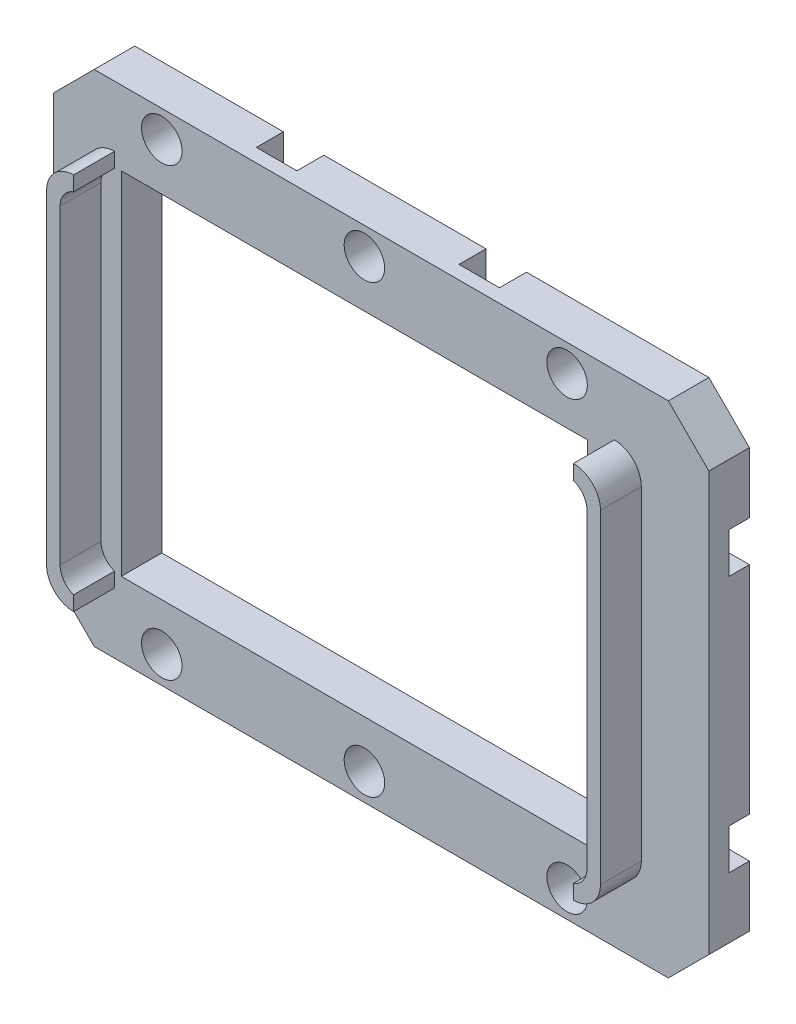
SolidWorks part; units mm, degrees
ref_plane "前视基准面" through (0, 0, 0) normal (0, 0, 1) x (1, 0, 0)
ref_plane "上视基准面" through (0, 0, 0) normal (0, 1, 0) x (1, 0, 0)
ref_plane "右视基准面" through (0, 0, 0) normal (1, 0, 0) x (0, 0, -1)
ref_plane "基准面4" through (0, 0, -11) normal (0, 0, 1) x (1, 0, 0)
sketch "草图1" plane through (0, 0, -11) normal (0, 0, 1) x (1, 0, 0)
  line L0 (-23, -18.5) -> (25.5, -18.5)
  line L1 (25.5, -18.5) -> (25.5, 18.5)
  line L2 (25.5, 18.5) -> (-23, 18.5)
  line L3 (-23, 18.5) -> (-23, -18.5)
extrude "凸台-拉伸1" add sketch "草图1" against normal blind 3
sketch "草图2" plane through (0, 0, -14) normal (0, 0, -1) x (-1, 0, 0)
  line L0 (17.5, -13.0002) -> (17.5, -10.2132)
  line L1 (17.5, -10.2132) -> (-4.4207, -10.2132)
  line L2 (-4.4207, -10.2132) -> (-4.4207, -13.0002)
  line L3 (-4.4207, -13.0002) -> (17.5, -13.0002)
extrude "切除-拉伸1" cut sketch "草图2" against normal through all
sketch "草图6" plane through (0, 0, -14) normal (0, 0, -1) x (-1, 0, 0)
  line L0 (-4.4207, 13.0002) -> (-4.4207, 10.2132)
  line L1 (-4.4207, 10.2132) -> (17.5, 10.2132)
  line L2 (17.5, 10.2132) -> (17.5, 13.0002)
  line L3 (17.5, 13.0002) -> (-4.4207, 13.0002)
extrude "切除-拉伸5" cut sketch "草图6" against normal through all
sketch "草图7" plane through (0, 0, -11) normal (0, 0, 1) x (1, 0, 0)
  line L0 (-20.5, -12) -> (-20.5, 12)
  line L1 (-18.5, 14) -> (-18.5, 12.9142)
  line L2 (-19.5, 11.5) -> (-19.5, -11.5)
  line L3 (-18.5, -12.9142) -> (-18.5, -14)
  arc A0 (-18.5, -14) -> (-20.5, -12) centre (-18.5, -12) cw
  arc A1 (-20.5, 12) -> (-18.5, 14) centre (-18.5, 12) cw
  arc A2 (-18.5, 12.9142) -> (-19.5, 11.5) centre (-18, 11.5) ccw
  arc A3 (-19.5, -11.5) -> (-18.5, -12.9142) centre (-18, -11.5) ccw
extrude "凸台-拉伸2" add sketch "草图7" along normal blind 3.028
sketch "草图8" plane through (0, 0, -11) normal (0, 0, 1) x (1, 0, 0)
  line L0 (19.5, -11.5) -> (19.5, 11.5)
  line L1 (18.5, 12.9142) -> (18.5, 14)
  line L2 (20.5, 12) -> (20.5, -12)
  line L3 (18.5, -14) -> (18.5, -12.9142)
  arc A0 (18.5, -12.9142) -> (19.5, -11.5) centre (18, -11.5) ccw
  arc A1 (19.5, 11.5) -> (18.5, 12.9142) centre (18, 11.5) ccw
  arc A2 (18.5, 14) -> (20.5, 12) centre (18.5, 12) cw
  arc A3 (20.5, -12) -> (18.5, -14) centre (18.5, -12) cw
extrude "凸台-拉伸3" add sketch "草图8" along normal blind 3.028
hole_wizard "M4 间隙孔1" positions "草图10" profile "草图9" hole size "M4" standard "ANSI Metric"
sketch "草图10" plane through (0, 0, -11) normal (0, 0, 1) x (1, 0, 0)
  point P0 (12.25, 6)
sketch "草图9" plane through (12.25, 6, -11) normal (1, 0, 0) x (0, -1, 0)
  line L0 (0, 0) -> (0, 3)
  line L1 (0, 3) -> (2.2235, 3)
  line L2 (2.2235, 3) -> (2.2235, 0)
  line L5 (2.2235, 0) -> (0, 0)
  line L11 (0, -6.35) -> (0, 107.95) construction
  dimension "通孔孔直径" = 4.447
  dimension "通孔孔深度" = 3
hole_wizard "Ø3.0 (3) 直径孔1" positions "草图12" profile "草图11" hole size "Ø3.0" standard "ANSI Metric"
sketch "草图12" plane through (0, 0, -14) normal (0, 0, -1) x (-1, 0, 0)
  point P0 (-15, -16.5)
  point P1 (15, -16.5)
  point P2 (0, -16.5)
  point P3 (-15, 16.5)
  point P4 (15, 16.5)
  point P5 (0, 16.5)
sketch "草图11" plane through (15, -16.5, -14) normal (1, 0, 0) x (0, 1, 0)
  line L0 (0, 0) -> (0, 6.028)
  line L1 (0, 6.028) -> (1.5, 6.028)
  line L2 (1.5, 6.028) -> (1.5, 0)
  line L5 (1.5, 0) -> (0, 0)
  line L11 (0, -6.35) -> (0, 107.95) construction
  dimension "通孔孔直径" = 3
  dimension "通孔孔深度" = 6.028
sketch "草图13" plane through (0, 0, -14) normal (0, 0, -1) x (-1, 0, 0)
  line L5 (23, 18.5) -> (23, -18.5) construction
  line L6 (-16.5, -13.0002) -> (18, -13.0002)
  line L7 (-16.5, -13.0002) -> (-16.5, 13.0002)
  line L8 (-16.5, 13.0002) -> (18, 13.0002)
  line L9 (18, -13.0002) -> (18, 13.0002)
  line L10 (-16.5, -13.0002) -> (18, 13.0002) construction
  line L11 (-16.5, 13.0002) -> (18, -13.0002) construction
  line L12 (-25.5, -18.5) -> (-25.5, 18.5) construction
  line L13 (17.5, 13.0002) -> (-4.4207, 13.0002) construction
  point P0 (0.75, 0)
  point P6 (3.06, 0)
  point P7 (1.8478, 0)
  dimension "D2" = 5
  dimension "D3" = 9
extrude "切除-拉伸7" cut sketch "草图13" against normal mid plane 20
chamfer "倒角1" distance 3 angle 45 4 edges at (-23, -18.5, -12.5) (-23, 18.5, -12.5) (25.5, 18.5, -12.5) (25.5, -18.5, -12.5)
sketch "草图14" plane through (0, 0, -14) normal (0, 0, -1) x (-1, 0, 0)
  line L0 (-15, -16.5) -> (0, -16.5) construction
  line L7 (-9, -14.5) -> (-9, -18.5)
  line L8 (-9, -14.5) -> (-6, -14.5)
  line L9 (-9, -18.5) -> (-6, -18.5)
  line L10 (-6, -14.5) -> (-6, -18.5)
  line L11 (-9, -14.5) -> (-6, -18.5) construction
  line L12 (-9, -18.5) -> (-6, -14.5) construction
  line L14 (0, 3.3154) -> (0, -3.3154) construction
  line L15 (9, -18.5) -> (6, -14.5) construction
  line L16 (9, -14.5) -> (6, -18.5) construction
  line L17 (6, -14.5) -> (6, -18.5)
  line L18 (9, -18.5) -> (6, -18.5)
  line L19 (9, -14.5) -> (6, -14.5)
  line L20 (9, -14.5) -> (9, -18.5)
  line L21 (3.3154, 0) -> (-3.3154, 0) construction
  line L22 (9, 14.5) -> (6, 18.5) construction
  line L23 (9, 18.5) -> (6, 14.5) construction
  line L24 (-9, 18.5) -> (-6, 14.5) construction
  line L25 (-9, 14.5) -> (-6, 18.5) construction
  line L26 (9, 14.5) -> (9, 18.5)
  line L27 (9, 14.5) -> (6, 14.5)
  line L28 (9, 18.5) -> (6, 18.5)
  line L29 (6, 14.5) -> (6, 18.5)
  line L30 (-6, 14.5) -> (-6, 18.5)
  line L31 (-9, 18.5) -> (-6, 18.5)
  line L32 (-9, 14.5) -> (-6, 14.5)
  line L33 (-9, 14.5) -> (-9, 18.5)
  point P2 (-7.5, -16.5)
  point P3 (-7.1261, -16.5)
  point P4 (-7.5, -16.5)
  point P5 (-10.1599, -16.5)
  point P7 (0, -16.5)
  point P21 (7.5, -16.5)
  point P30 (7.5, 16.5)
  point P31 (-7.5, 16.5)
  dimension "D1" = 3
  dimension "D2" = 4
extrude "切除-拉伸8" cut sketch "草图14" against normal blind 2
chamfer "倒角2" distance 3 angle 53 4 edges at (-7.5, 14.5, -12) (7.5, 14.5, -12) (-7.5, -14.5, -12) (7.5, -14.5, -12) first distance on face at (-7.5, 14.5, -13) first distance on face at (7.5, 14.5, -13) first distance on face at (-7.5, -14.5, -13) first distance on face at (7.5, -14.5, -13)
sketch "草图15" plane through (0, 0, -14) normal (0, 0, -1) x (-1, 0, 0)
  line L0 (-25.5, -15.5) -> (-25.5, 15.5) construction
  line L1 (-25.5, -8) -> (-23.5, -8)
  line L2 (-25.5, -8) -> (-25.5, -11)
  line L3 (-25.5, -11) -> (-23.5, -11)
  line L4 (-23.5, -8) -> (-23.5, -11)
  line L5 (3.3154, 0) -> (-3.3154, 0) construction
  line L6 (-23.5, 8) -> (-23.5, 11)
  line L7 (-25.5, 11) -> (-23.5, 11)
  line L8 (-25.5, 8) -> (-25.5, 11)
  line L9 (-25.5, 8) -> (-23.5, 8)
  line L11 (-25.5, -15.5) -> (23, -15.5) construction
  line L12 (-1.25, -15.5) -> (-1.25, 18.5) construction
  line L13 (-6, 18.5) -> (6, 18.5) construction
  line L14 (23, 8) -> (21, 8)
  line L15 (23, 8) -> (23, 11)
  line L16 (23, 11) -> (21, 11)
  line L17 (21, 8) -> (21, 11)
  line L18 (21, -8) -> (21, -11)
  line L19 (23, -11) -> (21, -11)
  line L20 (23, -8) -> (23, -11)
  line L21 (23, -8) -> (21, -8)
  dimension "D1" = 8
  dimension "D2" = 3
  dimension "D3" = 2
extrude "切除-拉伸9" cut sketch "草图15" against normal blind 1.5
chamfer "倒角3" distance 2 angle 45 4 edges at (-21, 9.5, -12.5) (-21, -9.5, -12.5) (23.5, 9.5, -12.5) (23.5, -9.5, -12.5)
